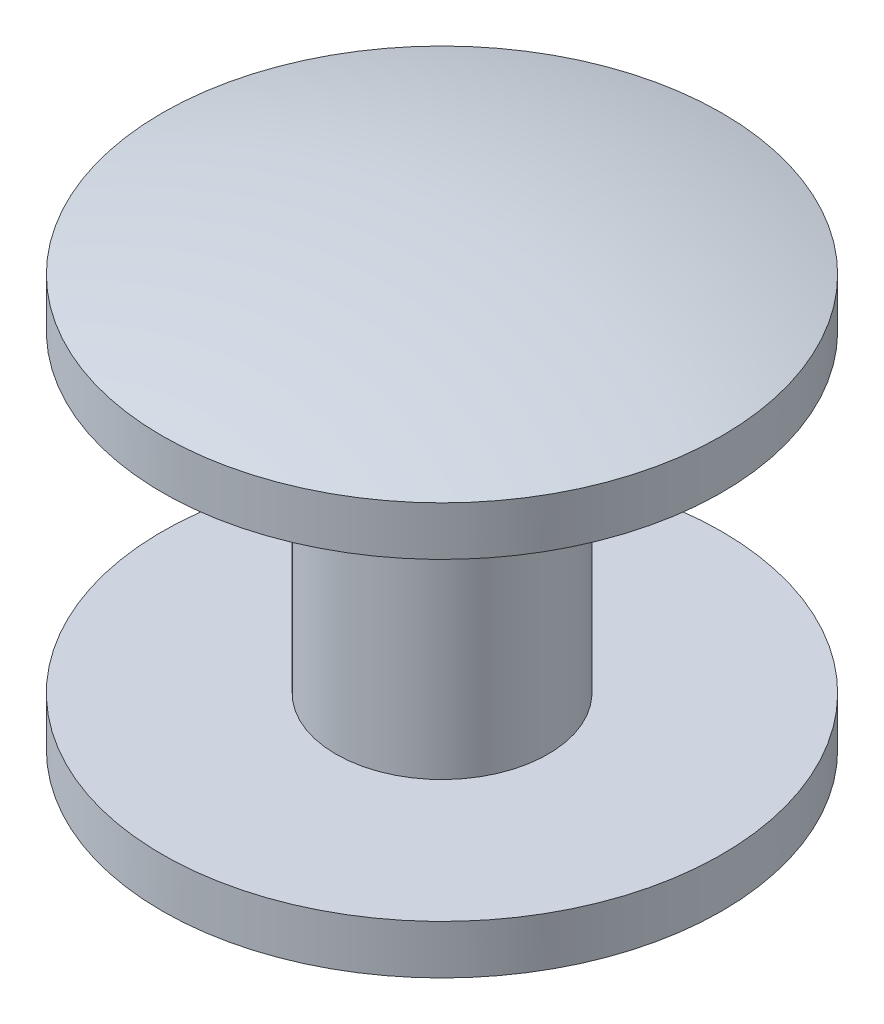
SolidWorks part; units mm, degrees
ref_plane "Front" through (0, 0, 0) normal (0, 0, 1) x (1, 0, 0)
ref_plane "Top" through (0, 0, 0) normal (0, 1, 0) x (1, 0, 0)
ref_plane "Right" through (0, 0, 0) normal (1, 0, 0) x (0, 0, -1)
sketch "Sketch1" plane through (0, 0, 0) normal (0, 1, 0) x (1, 0, 0)
  circle A0 centre (0, 0) radius 5.4117
  circle A1 centre (0, 0) radius 14.2787
  circle A2 centre (0, 0) radius 5.4117 construction
  circle A4 centre (0, 0) radius 14.2787 construction
extrude "Boss-Extrude1" add sketch "Sketch1" along normal mid plane 21 contours A0 | A1 A0 region at (0, 0, 0) region at (-13.8748, 0, 0)
extrude "Cut-Extrude1" cut sketch "Sketch1<3>" against normal mid plane 16 contours A1 A0 region at (-13.8748, 0, 0)
sketch "Sketch1<3>" plane through (0, 0, 0) normal (0, 1, 0) x (1, 0, 0) same geometry as "Sketch1"
dome "Dome1" faces to dome 1 distance 2 reverse direction no elliptical dome no face at (0, -10.5, 14.2787) parameters "D1"=2
dome "Dome2" faces to dome 1 distance 2 reverse direction no elliptical dome no face at (0, 10.5, 14.2787) parameters "D1"=2
